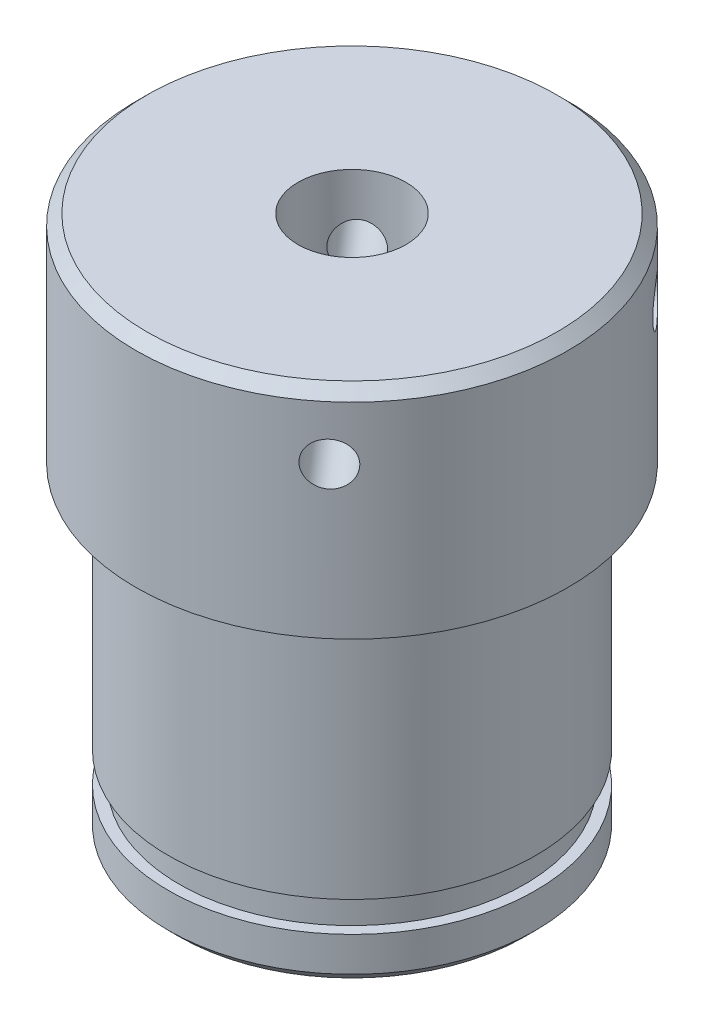
SolidWorks part; units mm, degrees
material "1060 Сплав"
ref_plane "Спереди" through (0, 0, 0) normal (0, 0, 1) x (1, 0, 0)
ref_plane "Сверху" through (0, 0, 0) normal (0, 1, 0) x (1, 0, 0)
ref_plane "Справа" through (0, 0, 0) normal (1, 0, 0) x (0, 0, -1)
sketch "Эскиз1" plane through (0, 0, 0) normal (0, 1, 0) x (1, 0, 0)
  circle A0 centre (0, 0) radius 8.5
  dimension "D1" = 17
extrude "Бобышка-Вытянуть1" add sketch "Эскиз1" along normal blind 15
sketch "Эскиз2" plane through (0, 15, 0) normal (0, 1, 0) x (1, 0, 0)
  circle A0 centre (0, 0) radius 10
  dimension "D1" = 20
extrude "Бобышка-Вытянуть2" add sketch "Эскиз2" along normal blind 10
sketch "Эскиз3" plane through (0, 0, 0) normal (0, -1, 0) x (1, 0, 0)
  circle A0 centre (0, 6) radius 1
  circle A1 centre (6, 0) radius 1
  circle A2 centre (0, -6) radius 1
  circle A3 centre (-6, 0) radius 1
  point P12 (0, 0)
  dimension "D1" = 2
  dimension "D2" = 6
  dimension "D3" = 4
extrude "Вырез-Вытянуть1" cut sketch "Эскиз3" against normal blind 10
sketch "Эскиз4" plane through (0, 0, 0) normal (0, -1, 0) x (1, 0, 0)
  circle A0 centre (0, 0) radius 8
  circle A1 centre (0, 0) radius 8.5
  dimension "D1" = 16
extrude "Вырез-Вытянуть2" cut sketch "Эскиз4" against normal blind 1.4 from offset 2.1 offset against normal yes
chamfer "Фаска1" distance 0.5 angle 45 2 edges at (0, 0, 8.5) (0, 25, 10)
sketch "Эскиз6" plane through (0, 25, 0) normal (0, 1, 0) x (1, 0, 0)
  line L0 (0, 12.2337) -> (0, -13.1957) construction
ref_plane "Плоскость1" through (6.5246, 0, 7.5782) normal (0.6525, 0, 0.7578) x (0.7578, 0, -0.6525)
sketch "Эскиз7" plane through (6.5246, 0, 7.5782) normal (0.6525, 0, 0.7578) x (0.7578, 0, -0.6525)
  line L0 (7.982, 25) -> (-8.6096, 25) construction
  circle A0 centre (0, 22) radius 1
  dimension "D1" = 2
  dimension "D2" = 3
extrude "Вырез-Вытянуть3" cut sketch "Эскиз7" against normal blind 8
pattern_circular "Круговой массив1" count 4 over 360 about axis through (0, 25, 0) along (0, -1, 0) of "Вырез-Вытянуть3"
sketch "Эскиз8" plane through (0, 0, 0) normal (0, -1, 0) x (1, 0, 0)
  circle A0 centre (0, 0) radius 3.5
  dimension "D1" = 7
extrude "Вырез-Вытянуть4" cut sketch "Эскиз8" against normal blind 5.5
chamfer "Фаска2" distance 0.5 angle 45 1 edges at (0, 0, -3.5)
sketch "Эскиз9" plane through (0, 5.5, 0) normal (0, -1, 0) x (1, 0, 0)
  circle A0 centre (0, 0) radius 2.5
  dimension "D1" = 5
extrude "Вырез-Вытянуть5" cut sketch "Эскиз9" against normal up to next
